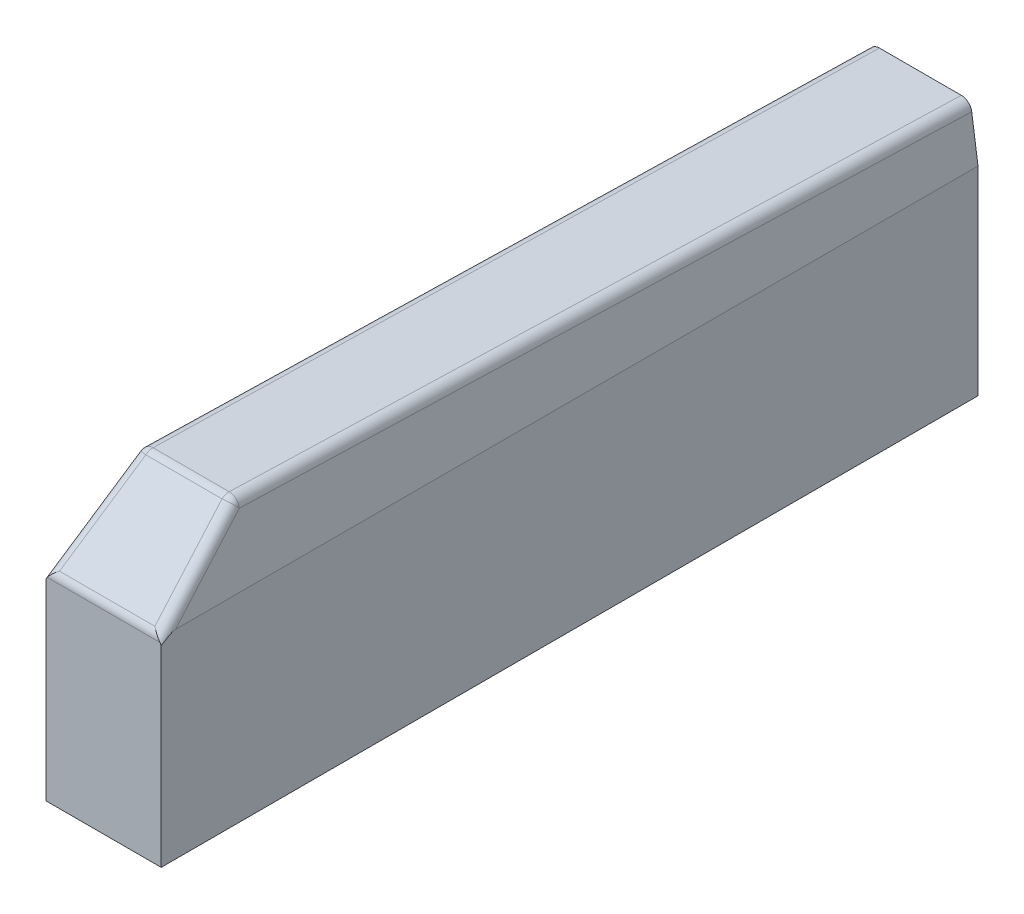
SolidWorks part; units mm, degrees
ref_plane "Alzado" through (0, 0, 0) normal (0, 0, 1) x (1, 0, 0)
ref_plane "Planta" through (0, 0, 0) normal (0, 1, 0) x (1, 0, 0)
ref_plane "Vista lateral" through (0, 0, 0) normal (1, 0, 0) x (0, 0, -1)
sketch "Croquis1" plane through (0, 0, 0) normal (0, 1, 0) x (1, 0, 0)
  line L1 (0, 0) -> (11, 0)
  line L2 (0, 0) -> (0, 78)
  line L3 (0, 78) -> (11, 78)
  line L4 (11, 0) -> (11, 78)
  dimension "D1" = 78
  dimension "D2" = 11
extrude "Saliente-Extruir1" add sketch "Croquis1" along normal blind 26
sketch "Croquis4" plane through (0, 0, 0) normal (0, 0, 1) x (1, 0, 0)
  line L0 (0, 26) -> (1, 26)
  line L1 (0, 26) -> (11, 26) construction
  line L2 (1, 26) -> (0, 19)
  line L3 (0, 26) -> (0, 0) construction
  line L4 (0, 19) -> (0, 26)
  line L5 (10, 26) -> (11, 26)
  line L6 (11, 26) -> (11, 19)
  line L7 (11, 26) -> (11, 0) construction
  line L8 (11, 19) -> (10, 26)
  dimension "D1" = 1
  dimension "D2" = 1
  dimension "D3" = 7
  dimension "D4" = 7
extrude "Cortar-Extruir3" cut sketch "Croquis4" against normal through all
sketch "Croquis6" plane through (0, 0, 0) normal (-1, 0, 0) x (0, 0, 1)
  line L0 (0, 19) -> (0, 26)
  line L2 (0, 26) -> (-8, 26)
  line L3 (-8, 26) -> (0, 19)
  dimension "D1" = 8
  dimension "D2" = 7
extrude "Cortar-Extruir6" cut sketch "Croquis6" against normal through all
sketch "Croquis8" plane through (0, 0, 0) normal (-1, 0, 0) x (0, 0, 1)
  line L1 (-80, 26) -> (-6.87, 26)
  line L5 (-80, 24) -> (-6.87, 26)
  line L6 (-80, 26) -> (-80, 24)
extrude "Cortar-Extruir7" cut sketch "Croquis8" against normal through all
fillet "Redondeo4" radius 1 6 edges at (0.8589, 25.0124, -42.9829) (0.4979, 22.485, -3.9829) (5.5, 25.97, -7.9658) (10.5021, 22.485, -3.9829) (10.1411, 25.0124, -42.9829) (5.5, 19, 0)
